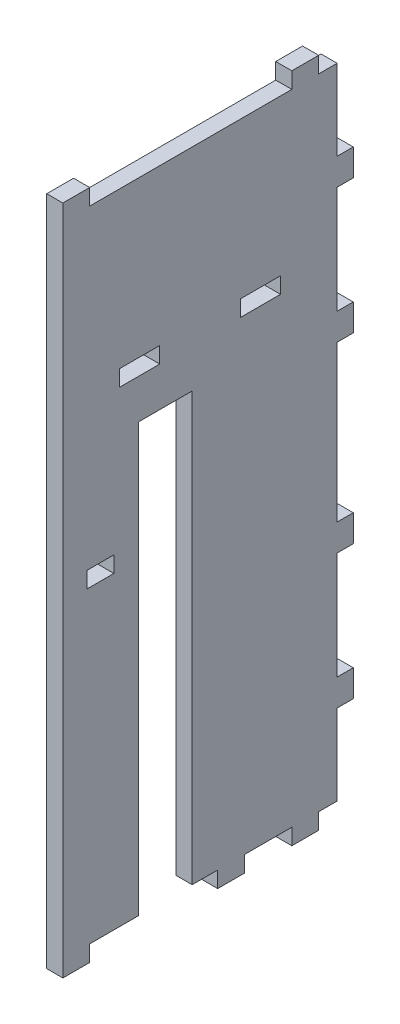
SolidWorks part; units mm, degrees
ref_plane "Plan de face" through (0, 0, 0) normal (0, 0, 1) x (1, 0, 0)
ref_plane "Plan de dessus" through (0, 0, 0) normal (0, 1, 0) x (1, 0, 0)
ref_plane "Plan de droite" through (0, 0, 0) normal (1, 0, 0) x (0, 0, -1)
sketch "Esquisse1" plane through (0, 0, 0) normal (1, 0, 0) x (0, 0, -1)
  line L0 (97.1531, 0) -> (-102.2664, 0) construction
  line L1 (-51.085, 119) -> (51.085, 119)
  line L2 (-51.085, 119) -> (-51.085, -119)
  line L3 (-51.085, -119) -> (51.085, -119)
  line L4 (51.085, 119) -> (51.085, -119)
  line L5 (0, 172.7153) -> (0, -236.1933) construction
  line L7 (-42.085, -4) -> (-32.085, -4)
  line L8 (-42.085, -4) -> (-42.085, 2)
  line L9 (-42.085, 2) -> (-32.085, 2)
  line L10 (-32.085, -4) -> (-32.085, 2)
  line L15 (-30, 61) -> (-15, 61)
  line L16 (-30, 61) -> (-30, 55)
  line L17 (-30, 55) -> (-15, 55)
  line L18 (-15, 61) -> (-15, 55)
  line L19 (15, 61) -> (30, 61)
  line L20 (15, 61) -> (15, 55)
  line L21 (15, 55) -> (30, 55)
  line L22 (30, 61) -> (30, 55)
  dimension "D1" = 238
  dimension "D2" = 102.17
  dimension "D4" = 119
  dimension "D13" = 15
  dimension "D14" = 15
  dimension "D15" = 30
  dimension "D16" = 6
  dimension "D17" = 6
  dimension "D3" = 51.085
  dimension "D5" = 58
  dimension "D6" = 21.085
  dimension "D7" = 10
  dimension "D8" = 6
  dimension "D9" = 9
  dimension "D10" = 117
extrude "Boss.-Extru.1" add sketch "Esquisse1" along normal blind 6
sketch "Esquisse3" plane through (6, 0, 0) normal (1, 0, 0) x (0, 0, -1)
  line L0 (-51.085, -119) -> (51.085, -119) construction
  line L1 (-51.085, -119) -> (-41.085, -119)
  line L2 (-51.085, -119) -> (-51.085, -125)
  line L3 (-51.085, -125) -> (-41.085, -125)
  line L4 (-41.085, -119) -> (-41.085, -125)
  line L5 (245.3741, 0) -> (-166.5298, 0) construction
  line L6 (51.085, -119) -> (51.085, 119) construction
  line L7 (34.205, -119) -> (44.205, -119)
  line L8 (34.205, -119) -> (34.205, -125)
  line L9 (34.205, -125) -> (44.205, -125)
  line L10 (0, 208.6671) -> (0, -232.3841) construction
  line L11 (-51.085, -119) -> (51.085, -119) construction
  line L12 (44.205, -119) -> (44.205, -125)
  line L13 (57.085, 39) -> (57.085, 29)
  line L14 (51.085, 29) -> (57.085, 29)
  line L15 (51.085, 39) -> (51.085, 29)
  line L16 (51.085, 39) -> (57.085, 39)
  line L17 (57.085, 89) -> (57.085, 79)
  line L18 (51.085, 79) -> (57.085, 79)
  line L19 (51.085, 89) -> (51.085, 79)
  line L20 (51.085, 89) -> (57.085, 89)
  line L22 (51.085, -89) -> (57.085, -89)
  line L23 (51.085, -89) -> (51.085, -79)
  line L24 (51.085, -79) -> (57.085, -79)
  line L25 (57.085, -89) -> (57.085, -79)
  line L26 (51.085, -39) -> (57.085, -39)
  line L27 (51.085, -39) -> (51.085, -29)
  line L28 (51.085, -29) -> (57.085, -29)
  line L29 (0, -208.6671) -> (0, 232.3841) construction
  line L30 (6.585, -119) -> (16.585, -119)
  line L31 (6.585, -119) -> (6.585, -125)
  line L32 (6.585, -125) -> (16.585, -125)
  line L33 (16.585, -119) -> (16.585, -125)
  line L35 (57.085, -39) -> (57.085, -29)
  line L46 (44.205, 119) -> (44.205, 125)
  line L47 (34.205, 125) -> (44.205, 125)
  line L48 (34.205, 119) -> (34.205, 125)
  line L49 (34.205, 119) -> (44.205, 119)
  line L50 (-41.085, 119) -> (-41.085, 125)
  line L51 (-51.085, 125) -> (-41.085, 125)
  line L52 (-51.085, 119) -> (-51.085, 125)
  line L53 (-51.085, 119) -> (-41.085, 119)
  dimension "D2" = 10
  dimension "D3" = 6
  dimension "D4" = 10
  dimension "D5" = 6.88
  dimension "D6" = 6
  dimension "D7" = 6
  dimension "D8" = 10
  dimension "D9" = 6
  dimension "D10" = 10
  dimension "D11" = 6
  dimension "D12" = 10
  dimension "D13" = 17.62
  dimension "D14" = 30
  dimension "D15" = 40
extrude "Boss.-Extru.5" add sketch "Esquisse3" against normal blind 6
sketch "Esquisse6" plane through (6, 0, 0) normal (1, 0, 0) x (0, 0, -1)
  line L0 (-41.085, -119) -> (6.585, -119) construction
  line L1 (-22.915, -119) -> (-2.915, -119)
  line L2 (-22.915, -119) -> (-22.915, 40.29)
  line L3 (-22.915, 40.29) -> (-2.915, 40.29)
  line L4 (-2.915, -119) -> (-2.915, 40.29)
  line L5 (51.085, -79) -> (51.085, -39) construction
  line L6 (-41.085, 125) -> (-51.085, 125) construction
  dimension "D1" = 20
  dimension "D2" = 84.71
  dimension "D3" = 54
extrude "Enlèv. mat.-Extru.2" cut sketch "Esquisse6" against normal blind 6
equation "\"D3@Esquisse1\"=\"D2@Esquisse1\"/2"
equation "\"D4@Esquisse1\"=\"D1@Esquisse1\"/2"
